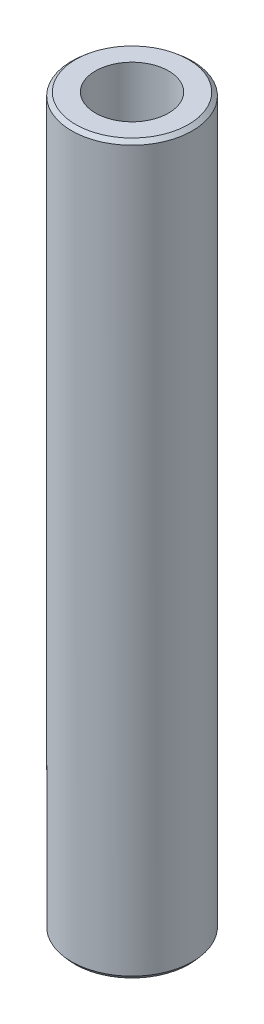
SolidWorks part; units mm, degrees
ref_plane "Front Plane" through (0, 0, 0) normal (0, 0, 1) x (1, 0, 0)
ref_plane "Top Plane" through (0, 0, 0) normal (0, 1, 0) x (1, 0, 0)
ref_plane "Right Plane" through (0, 0, 0) normal (1, 0, 0) x (0, 0, -1)
sketch "Sketch1" plane through (0, 0, 0) normal (0, 1, 0) x (1, 0, 0)
  circle A0 centre (0, 0) radius 12.5
  dimension "SHAFT_OD" = 25
extrude "Boss-Extrude1" add sketch "Sketch1" along normal blind 150.4668
sketch "Sketch2" plane through (0, 0, 0) normal (0, 1, 0) x (1, 0, 0)
  circle A0 centre (0, 0) radius 7.5672
  dimension "BORE_D" = 15.1344
extrude "Cut-Extrude1" cut sketch "Sketch2" along normal through all
chamfer "Chamfer1" distance 0.7073 angle 49.56 2 edges at (0, 150.4668, 12.5) (0, 0, 12.5) first distance on face at (0, 150.4668, 12.5) first distance on face at (0, 0, 7.5672)
